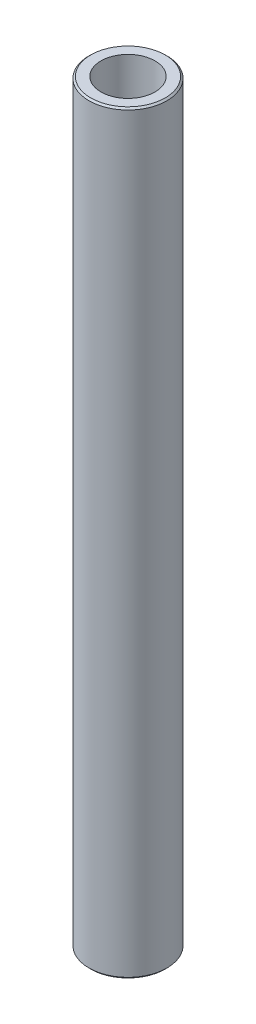
SolidWorks part; units mm, degrees
ref_plane "Front Plane" through (0, 0, 0) normal (0, 0, 1) x (1, 0, 0)
ref_plane "Top Plane" through (0, 0, 0) normal (0, 1, 0) x (1, 0, 0)
ref_plane "Right Plane" through (0, 0, 0) normal (1, 0, 0) x (0, 0, -1)
sketch "Sketch1" plane through (0, 0, 0) normal (0, 1, 0) x (1, 0, 0)
  circle A0 centre (0, 0) radius 10
  dimension "SHAFT_OD" = 20
extrude "Boss-Extrude1" add sketch "Sketch1" along normal blind 193.6939
sketch "Sketch2" plane through (0, 0, 0) normal (0, 1, 0) x (1, 0, 0)
  circle A0 centre (0, 0) radius 6.9341
  dimension "BORE_D" = 13.8682
extrude "Cut-Extrude1" cut sketch "Sketch2" along normal through all
chamfer "Chamfer1" distance 0.4137 angle 46.583 2 edges at (0, 193.6939, 10) (0, 0, 10) first distance on face at (0, 193.6939, 10) first distance on face at (0, 0, 6.9341)
